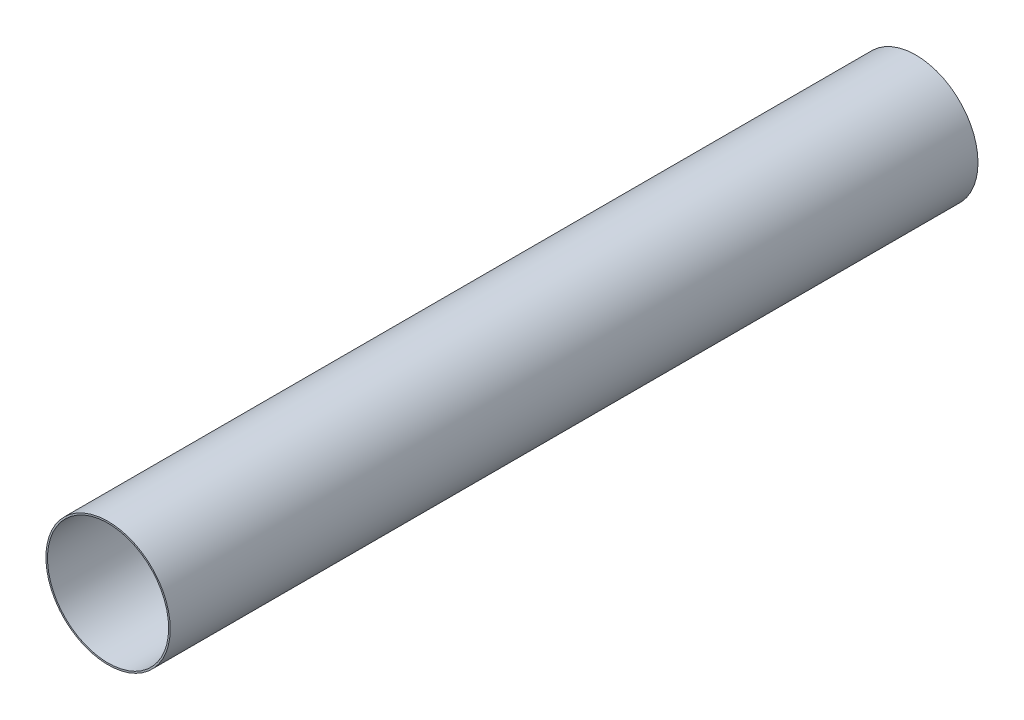
SolidWorks part; units mm, degrees
material "Thornel Mat VMA"
ref_plane "Front Plane" through (0, 0, 0) normal (0, 0, 1) x (1, 0, 0)
ref_plane "Top Plane" through (0, 0, 0) normal (0, 1, 0) x (1, 0, 0)
ref_plane "Right Plane" through (0, 0, 0) normal (1, 0, 0) x (0, 0, -1)
sketch "Sketch1" plane through (0, 0, 0) normal (0, 0, 1) x (1, 0, 0)
  circle A0 centre (0, 0) radius 78.2
  circle A1 centre (0, 0) radius 76.2
  dimension "D1" = 152.4
  dimension "D2" = 156.4
extrude "Boss-Extrude1" add sketch "Sketch1" along normal mid plane 1016
equation "\"TubeDiameter\" = 6.000in"
equation "\"D1@Sketch1\"=\"TubeDiameter\""
equation "\"D2@Sketch1\"=\"TubeDiameter\"+4mm"
